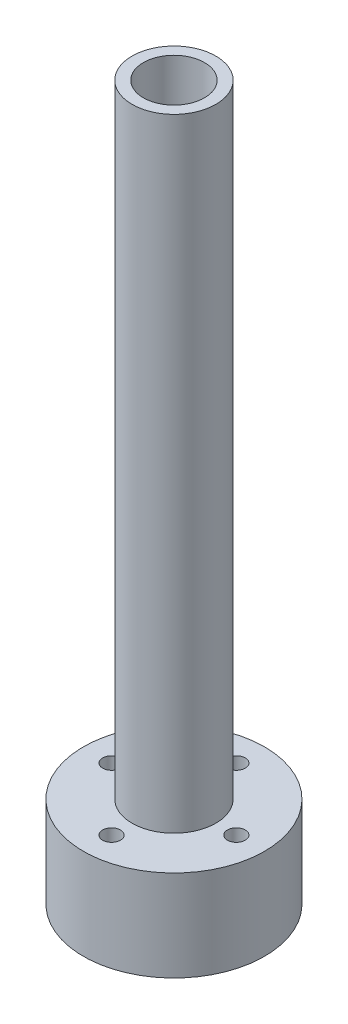
SolidWorks part; units mm, degrees
ref_plane "Front Plane" through (0, 0, 0) normal (0, 0, 1) x (1, 0, 0)
ref_plane "Top Plane" through (0, 0, 0) normal (0, 1, 0) x (1, 0, 0)
ref_plane "Right Plane" through (0, 0, 0) normal (1, 0, 0) x (0, 0, -1)
sketch "Sketch1" plane through (0, 0, 0) normal (0, 1, 0) x (1, 0, 0)
  circle A0 centre (0, 0) radius 10.16
  circle A1 centre (7, 0) radius 1
  circle A2 centre (0, -7) radius 1
  circle A3 centre (-7, 0) radius 1
  circle A4 centre (0, 7) radius 1
  point P14 (0, 0)
  dimension "D1" = 20.32
  dimension "D2" = 2
  dimension "D3" = 7
  dimension "D4" = 4
extrude "Boss-Extrude1" add sketch "Sketch1" along normal blind 19.05
sketch "Sketch2" plane through (0, 19.05, 0) normal (0, 1, 0) x (1, 0, 0)
  circle A0 centre (0, 0) radius 4.699
  dimension "D1" = 9.398
extrude "Boss-Extrude2" add sketch "Sketch2" along normal blind 88.9 from surface starting at face at (0, 0, 10.16)
sketch "Sketch3" plane through (0, 88.9, 0) normal (0, 1, 0) x (1, 0, 0)
  circle A0 centre (0, 0) radius 3.429
  dimension "D1" = 6.858
extrude "Cut-Extrude1" cut sketch "Sketch3" against normal through all
sketch "Sketch4" plane through (0, 0, 0) normal (0, -1, 0) x (1, 0, 0)
  circle A1 centre (0, 0) radius 10.16
  circle A2 centre (0, 0) radius 10.16
  dimension "D1" = 0
extrude "Cut-Extrude2" cut sketch "Sketch4" against normal blind 8.842
equation "\"D3@Sketch1\"=7MM"
equation "\"D2@Sketch1\"=2MM"
equation "\"tightTol\"= 0.005in"
equation "\"normTol\"= 0.01in"
equation "\"looseTol\"= 0.02in"
equation "\"D1@Sketch2\"=0.375000-\"tightTol\""
equation "\"D1@Sketch3\"=1/4+\"looseTol\""
equation "\"D1@Cut-Extrude2\"= 15.7mm - 0.25 - \"looseTol\""
